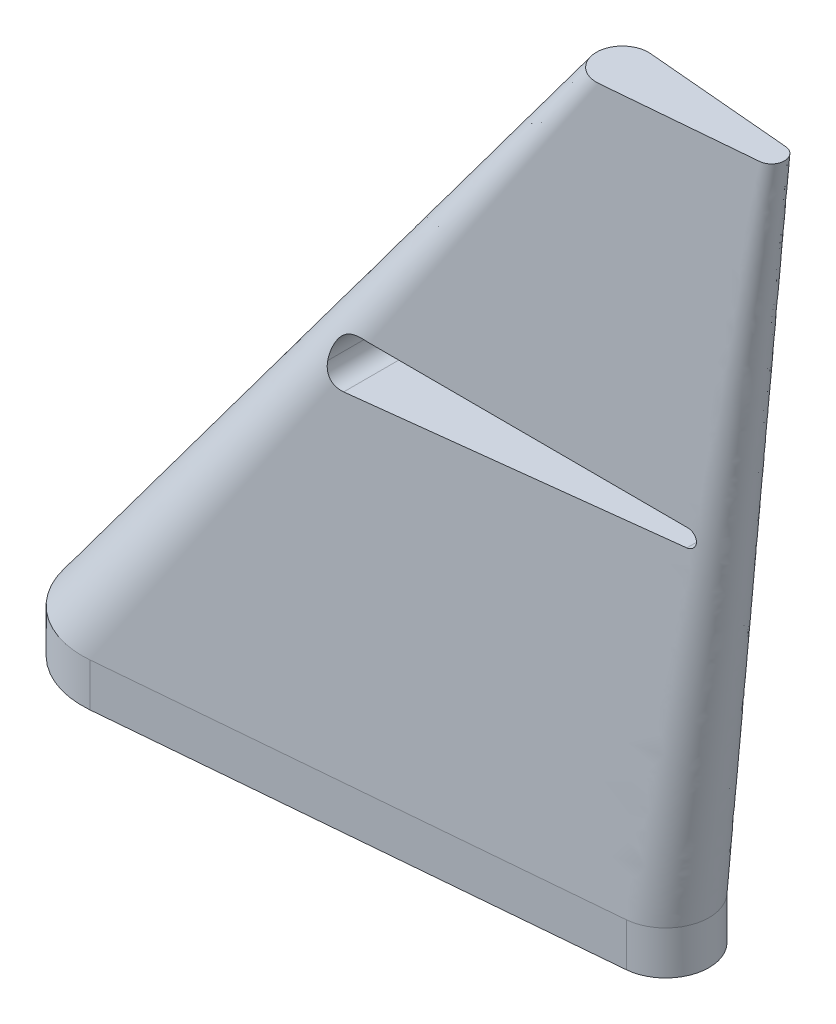
SolidWorks part; units mm, degrees
ref_plane "Front Plane" through (0, 0, 0) normal (0, 0, 1) x (1, 0, 0)
ref_plane "Top Plane" through (0, 0, 0) normal (0, 1, 0) x (1, 0, 0)
ref_plane "Right Plane" through (0, 0, 0) normal (1, 0, 0) x (0, 0, -1)
sketch "Sketch1" plane through (0, 0, 0) normal (0, 1, 0) x (1, 0, 0)
  line L0 (2.7614, 2.5303) -> (17.2223, 1.2652)
  line L1 (0, 0) -> (18.3816, 0) construction
  line L2 (0, -2.5303) -> (0, 2.5303) construction
  line L3 (0, 2.5303) -> (2.7614, 2.5303) construction
  line L4 (17.2223, 1.2652) -> (18.3816, 1.2652) construction
  line L5 (18.3816, 1.2652) -> (18.3816, -1.2652) construction
  line L6 (17.2223, -1.2652) -> (18.3816, -1.2652) construction
  line L7 (0, -2.5303) -> (2.7614, -2.5303) construction
  line L8 (2.7614, -2.5303) -> (17.2223, -1.2652)
  arc A0 (2.7614, -2.5303) -> (2.7614, 2.5303) centre (2.54, 0) cw
  arc A1 (17.2223, 1.2652) -> (17.2223, -1.2652) centre (17.1116, 0) cw
  point P3 (0, -2.0509)
  point P7 (1.6688, 1.4674)
  point P10 (17.7622, 0.9779)
  point P15 (1.4904, -1.2332)
  dimension "D1" = 1.27
  dimension "D3" = 2.54
  dimension "D2" = 5
extrude "Boss-Extrude1" add sketch "Sketch1" against normal blind 1.27
ref_plane "Plane2" through (0, 20.32, 0) normal (0, 1, 0) x (1, 0, 0)
sketch "Sketch5" plane through (0, 20.32, 0) normal (0, 1, 0) x (1, 0, 0)
  line L0 (0, 0) -> (18.3816, 0) construction
  line L1 (15.908, 0.7591) -> (20.2463, 0.3796)
  line L2 (20.2463, -0.3796) -> (15.908, -0.7591)
  arc A0 (2.7614, 2.5303) -> (2.7614, -2.5303) centre (2.54, 0) ccw construction
  arc A1 (17.2223, -1.2652) -> (17.2223, 1.2652) centre (17.1116, 0) ccw construction
  arc A2 (20.2463, 0.3796) -> (20.2463, -0.3796) centre (20.2131, 0) cw
  arc A3 (15.908, -0.7591) -> (15.908, 0.7591) centre (15.8416, 0) cw
  point P14 (0, 0)
  point P15 (0, 0)
  point P16 (15.5253, 0)
  point P17 (13.8443, 0)
  point P18 (15.908, 0)
  dimension "D1" = 0.762
  dimension "D2" = 0.381
  dimension "D3" = 5
  dimension "D4" = 2.54
loft "Loft2" add profiles "Sketch1<3>", "Sketch5" connector at (2.7614, 0, 2.5303) connector at (15.908, 20.32, 0.7591)
sketch "Sketch1<3>" plane through (0, 0, 0) normal (0, 1, 0) x (1, 0, 0) same geometry as "Sketch1"
sketch "Sketch7" plane through (0, 0, 0) normal (0, 0, 1) x (1, 0, 0)
  line L0 (7.5394, 10.16) -> (19.4883, 10.16) construction
  line L1 (18.3823, 0) -> (20.5943, 20.32) construction
  line L2 (15.079, 20.32) -> (-0.0001, 0) construction
  line L3 (9.914, 11.1721) -> (18.5905, 10.413)
  line L4 (18.5754, 9.9061) -> (9.3314, 9.6522)
  line L5 (8.8094, 10.16) -> (8.8094, 8.2865) construction
  arc A0 (8.8094, 10.16) -> (9.914, 11.1721) centre (9.8254, 10.16) cw
  arc A1 (18.5905, 10.413) -> (18.5754, 9.9061) centre (18.5684, 10.16) cw
  arc A2 (9.3314, 9.6522) -> (8.8094, 10.16) centre (9.3174, 10.16) cw
  point P15 (8.9449, 10.16)
  point P16 (10.3225, 11.5197)
  point P18 (0, 0)
  point P19 (10.5096, 9.3929)
  point P20 (11.2048, 11.1399)
  point P21 (9.4232, 9.6522)
  dimension "D3" = 0.254
  dimension "D4" = 1.016
  dimension "D5" = 0.508
  dimension "D1" = 10.16
  dimension "D2" = 5
  dimension "D6" = 1.778
extrude "Cut-Extrude1" cut sketch "Sketch7" against normal through all both and the other way through all
